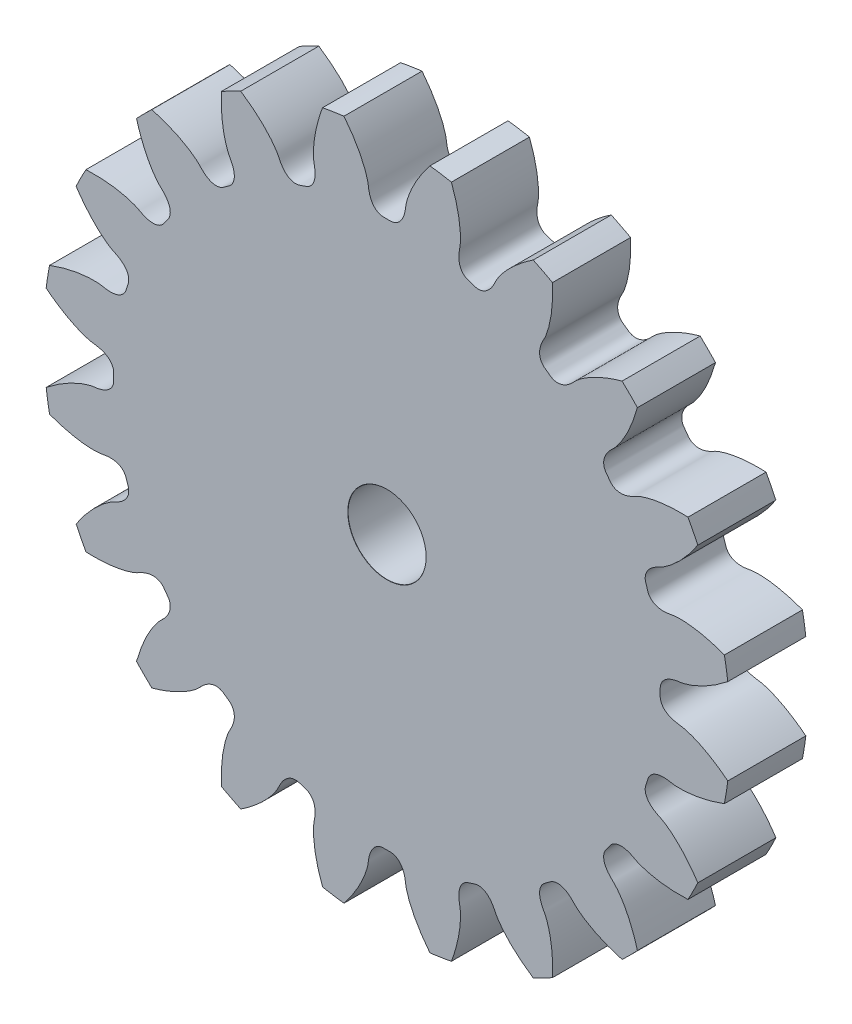
SolidWorks part; units mm, degrees
ref_plane "Front Plane" through (0, 0, 0) normal (0, 0, 1) x (1, 0, 0)
ref_plane "Top Plane" through (0, 0, 0) normal (0, 1, 0) x (1, 0, 0)
ref_plane "Right Plane" through (0, 0, 0) normal (1, 0, 0) x (0, 0, -1)
ref_axis "Axis1" through (0, 0, 55) along (0, 0, -1)
sketch "SketchRevolveSpur06" plane through (0, 0, 0) normal (1, 0, 0) x (0, 0, -1)
  line L0 (0, 0) -> (1, 0) construction
  line L1 (-2.5, 0) -> (-2.5, 22)
  line L2 (-2.5, 22) -> (2.5, 22)
  line L3 (2.5, 22) -> (2.5, 0)
  line L4 (2.5, 0) -> (-2.5, 0)
  dimension "Side1" = 2.5
  dimension "OutsideRadius" = 22
  dimension "Side2" = 2.5
revolve "Spur06" add sketch "SketchRevolveSpur06" angle 360 about L0
sketch "SketchToothSpur06" plane through (0, 0, 0) normal (0, 0, 1) x (1, 0, 0)
  arc A0 (21.9184, 2.8272) -> (21.9184, -2.8272) centre (0, 0) cw
  spline S0 degree 3 poles (21.9184, -2.8272) (21.7416, -2.6835) (21.4772, -2.4812) (21.1223, -2.2356) (20.8731, -2.0743) (20.6345, -1.9301) (20.4073, -1.8021) (20.1921, -1.6896) (19.9897, -1.5916) (19.8009, -1.5073) (19.6261, -1.4356) (19.4661, -1.3757) (19.3213, -1.3265) (19.1923, -1.2871) (19.0795, -1.2564) (18.9833, -1.2333) (18.904, -1.2169) (18.8204, -1.2019) (18.7434, -1.1939) (18.6685, -1.1847) (18.6117, -1.1764) (18.5561, -1.1671) (18.5017, -1.1568) (18.4483, -1.1454) (18.3959, -1.1329) (18.3446, -1.1193) (18.2943, -1.1046) (18.2449, -1.0886) (18.1965, -1.0714) (18.1488, -1.0529) (18.102, -1.033) (18.056, -1.0115) (18.0107, -0.9883) (17.9661, -0.9633) (17.9221, -0.9363) (17.8788, -0.9069) (17.8362, -0.875) (17.7943, -0.8402) (17.7532, -0.8022) (17.7133, -0.7606) (17.6747, -0.715) (17.638, -0.665) (17.6038, -0.6103) (17.5728, -0.5509) (17.5459, -0.4866) (17.5241, -0.4179) (17.5085, -0.3455) (17.5004, -0.2759) (17.4969, -0.1605) (17.5024, 0) (17.4969, 0.1605) (17.5004, 0.2759) (17.5085, 0.3455) (17.5241, 0.4179) (17.5459, 0.4866) (17.5728, 0.5509) (17.6038, 0.6103) (17.638, 0.665) (17.6747, 0.715) (17.7133, 0.7606) (17.7532, 0.8022) (17.7943, 0.8402) (17.8362, 0.875) (17.8788, 0.9069) (17.9221, 0.9363) (17.9661, 0.9633) (18.0107, 0.9883) (18.056, 1.0115) (18.102, 1.033) (18.1488, 1.0529) (18.1965, 1.0714) (18.2449, 1.0886) (18.2943, 1.1046) (18.3446, 1.1193) (18.3959, 1.1329) (18.4483, 1.1454) (18.5017, 1.1568) (18.5561, 1.1671) (18.6117, 1.1764) (18.6685, 1.1847) (18.7434, 1.1939) (18.8204, 1.2019) (18.904, 1.2169) (18.9833, 1.2333) (19.0795, 1.2564) (19.1923, 1.2871) (19.3213, 1.3265) (19.4661, 1.3757) (19.6261, 1.4356) (19.8009, 1.5073) (19.9897, 1.5916) (20.1921, 1.6896) (20.4073, 1.8021) (20.6345, 1.9301) (20.8731, 2.0743) (21.1223, 2.2356) (21.4772, 2.4812) (21.7416, 2.6835) (21.9184, 2.8272) knots 0 0 0 0 0.061397 0.089672 0.116331 0.141374 0.164802 0.186614 0.20681 0.225391 0.242356 0.257705 0.271438 0.283556 0.294058 0.302944 0.310215 0.31587 0.325834 0.331073 0.336221 0.341283 0.346263 0.351165 0.355997 0.360763 0.365471 0.370128 0.374745 0.37933 0.383895 0.388453 0.393018 0.397607 0.402237 0.406928 0.411702 0.416584 0.421598 0.426769 0.432124 0.437685 0.443471 0.449491 0.455745 0.462217 0.468878 0.475679 0.481075 0.5 0.518925 0.524321 0.531122 0.537783 0.544255 0.550509 0.556529 0.562315 0.567876 0.573231 0.578402 0.583416 0.588298 0.593072 0.597763 0.602393 0.606982 0.611547 0.616105 0.62067 0.625255 0.629872 0.634529 0.639237 0.644003 0.648835 0.653737 0.658717 0.663779 0.668927 0.674166 0.68413 0.689785 0.697056 0.705942 0.716444 0.728562 0.742295 0.757644 0.774609 0.79319 0.813386 0.835198 0.858626 0.883669 0.910328 0.938603 1 1 1 1
extrude "ToothExtrudeCutSpur06" cut sketch "SketchToothSpur06" against normal blind 2.5 and the other way blind 2.5
pattern_circular "PatternSpur06" count 20 every 18 about axis through (0, 0, 55) along (0, 0, -1) of "ToothExtrudeCutSpur06"
sketch "BoreRevolveSketch" plane through (0, 0, 0) normal (1, 0, 0) x (0, 0, -1)
  line L0 (0, 0) -> (1, 0) construction
  line L1 (-2.5, 0) -> (2.5, 0)
  line L2 (2.5, 0) -> (2.5, 2.51)
  line L3 (2.5, 2.51) -> (2.49, 2.5)
  line L4 (2.49, 2.5) -> (-2.49, 2.5)
  line L5 (-2.49, 2.5) -> (-2.5, 2.51)
  line L6 (-2.5, 2.51) -> (-2.5, 0)
  dimension "BoreSide1" = 2.5
  dimension "TaperSide1" = 2.51
  dimension "Chamfer1X" = 0.01
  dimension "Chamfer1Y" = 0.01
  dimension "BoreSide2" = 2.5
  dimension "TaperSide2" = 2.51
revolve "BoreRevolveCut" cut sketch "BoreRevolveSketch" angle 360 about L0
sketch "AuxiliarySketchSpur06" plane through (0, 0, 0) normal (0, 0, 1) x (1, 0, 0)
  circle A0 centre (0, 0) radius 20 construction
  circle A1 centre (0, 0) radius 18.7939 construction
  circle A2 centre (0, 0) radius 18.8063 construction
  circle A3 centre (0, 0) radius 22 construction
  circle A4 centre (0, 0) radius 17.5 construction
  dimension "PitchDiameter" = 40
  dimension "BaseDiameter" = 37.5877
  dimension "FormDiameter" = 37.6127
  dimension "MajorDiameter" = 44
  dimension "MinorDiameter" = 35
